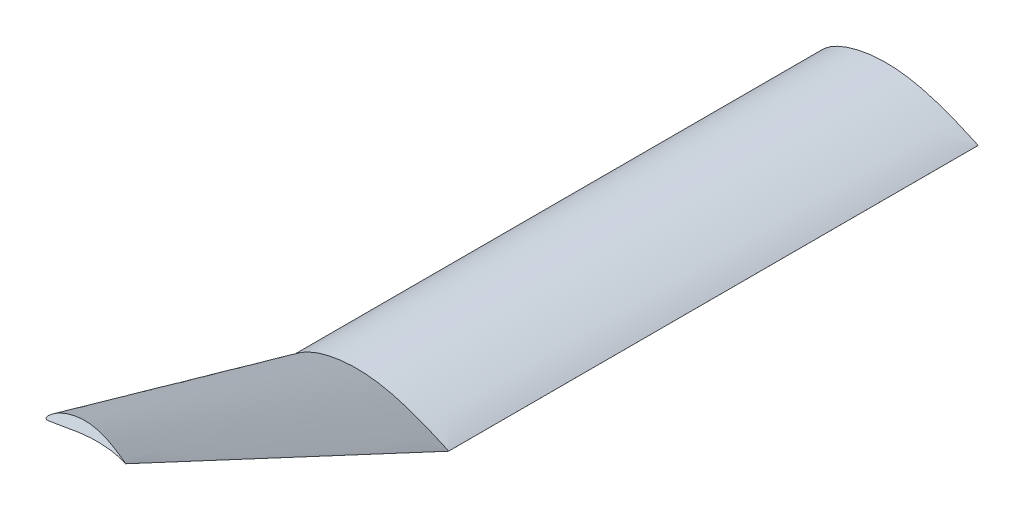
SolidWorks part; units mm, degrees
ref_plane "Front Plane" through (0, 0, 0) normal (0, 0, 1) x (1, 0, 0)
ref_plane "Top Plane" through (0, 0, 0) normal (0, 1, 0) x (1, 0, 0)
ref_plane "Right Plane" through (0, 0, 0) normal (1, 0, 0) x (0, 0, -1)
curve "Curve1"
curve "Curve6"
curve "Curve7"
curve "Curve8"
sketch "Sketch3" plane through (0, 0, 0) normal (0, 0, 1) x (1, 0, 0)
  line L0 (0, 0) -> (50, 0) construction
  line L1 (0.2298, 0.0405) -> (0.2298, 0.0158) construction
  line L2 (0.1804, 0.0405) -> (0.2298, 0.0405)
  line L3 (0.1804, 0.0405) -> (0.1804, -0.0089)
  line L4 (0.1804, -0.0089) -> (0.2298, -0.0089)
  line L5 (0.2298, 0.0405) -> (0.2298, -0.0089)
  line L6 (0.4642, 0.0242) -> (0.4889, 0.0242)
  line L7 (0.4642, 0.0242) -> (0.4642, -0.0005)
  line L8 (0.4642, -0.0005) -> (0.4889, -0.0005)
  line L9 (0.4889, 0.0242) -> (0.4889, -0.0005)
  line L10 (0.2298, 0.0158) -> (0.2146, 0.0158) construction
  line L11 (0.2146, 0.0158) -> (0.2146, 0.0405) construction
  line L12 (0.2146, 0.0405) -> (0.2298, 0.0405) construction
  line L13 (0, 0) -> (500, 0) construction
  line L14 (0.1804, 0.0458) -> (0.1804, -0.0178) construction
  line L15 (0, 0) -> (0, -165.9812) construction
  line L16 (0, -165.9812) -> (300, -165.9812) construction
  line L17 (72.7802, 36.2202) -> (92.7802, 36.2202) construction
  line L18 (70.2802, 13.7202) -> (95.2802, 13.7202)
  line L19 (70.2802, 13.7202) -> (70.2802, 38.7202)
  line L20 (70.2802, 38.7202) -> (95.2802, 38.7202)
  line L21 (95.2802, 13.7202) -> (95.2802, 38.7202)
  line L22 (92.7802, 16.2202) -> (92.7802, 36.2202) construction
  line L23 (72.7802, 16.2202) -> (92.7802, 16.2202) construction
  line L24 (72.7802, 16.2202) -> (72.7802, 36.2202) construction
  line L25 (300, -0.018) -> (300, 0.015)
  line L26 (172.9506, 31.8748) -> (182.9506, 31.8748)
  line L27 (172.9506, 31.8748) -> (172.9506, 21.8748)
  line L28 (172.9506, 21.8748) -> (182.9506, 21.8748)
  line L29 (182.9506, 31.8748) -> (182.9506, 21.8748)
  spline S0 degree 3 poles (1.0002, -0.0023) (1, 0) (1.0002, 0.0023) (0.9919, 0.0001) (0.9849, 0.0027) (0.9729, 0.003) (0.9609, 0.0043) (0.9483, 0.0054) (0.9357, 0.0065) (0.9231, 0.0077) (0.9104, 0.0088) (0.8978, 0.01) (0.8852, 0.0111) (0.8725, 0.0123) (0.8599, 0.0134) (0.8473, 0.0146) (0.8347, 0.0157) (0.8221, 0.0168) (0.8094, 0.0179) (0.7968, 0.019) (0.7842, 0.0201) (0.7716, 0.0211) (0.759, 0.0222) (0.7464, 0.0232) (0.7337, 0.0243) (0.7211, 0.0253) (0.7085, 0.0263) (0.6959, 0.0273) (0.6833, 0.0283) (0.6706, 0.0293) (0.658, 0.0303) (0.6454, 0.0313) (0.6328, 0.0322) (0.6202, 0.0331) (0.6076, 0.0341) (0.595, 0.035) (0.5823, 0.0358) (0.5697, 0.0367) (0.5571, 0.0375) (0.5446, 0.0384) (0.532, 0.0392) (0.5194, 0.0399) (0.5068, 0.0407) (0.4942, 0.0414) (0.4816, 0.0421) (0.469, 0.0427) (0.4565, 0.0434) (0.4439, 0.044) (0.4313, 0.0445) (0.4188, 0.0451) (0.4062, 0.0456) (0.3936, 0.046) (0.3811, 0.0464) (0.3685, 0.0468) (0.356, 0.0472) (0.3435, 0.0475) (0.3309, 0.0477) (0.3184, 0.0479) (0.3059, 0.0481) (0.2934, 0.0482) (0.2809, 0.0482) (0.2685, 0.0482) (0.256, 0.0481) (0.2436, 0.0479) (0.2312, 0.0477) (0.2189, 0.0474) (0.2065, 0.047) (0.1942, 0.0465) (0.182, 0.0459) (0.1698, 0.0452) (0.1576, 0.0444) (0.1456, 0.0434) (0.1336, 0.0423) (0.1217, 0.0411) (0.1099, 0.0397) (0.0983, 0.038) (0.0868, 0.0362) (0.0756, 0.0342) (0.0647, 0.0319) (0.0541, 0.0294) (0.0441, 0.0266) (0.0348, 0.0236) (0.0266, 0.0205) (0.0197, 0.0175) (0.0142, 0.0146) (0.0101, 0.012) (0.007, 0.0098) (0.0047, 0.0078) (0.003, 0.006) (0.0018, 0.0045) (0.0009, 0.003) (0.0003, 0.0017) (0, 0.0004) (0, -0.0008) (0.0005, -0.0021) (0.0015, -0.0032) (0.0028, -0.0043) (0.0046, -0.0054) (0.0068, -0.0066) (0.0097, -0.0078) (0.0135, -0.0091) (0.0186, -0.0106) (0.0252, -0.0121) (0.0334, -0.0135) (0.043, -0.0148) (0.0536, -0.0159) (0.0648, -0.0167) (0.0764, -0.0173) (0.0882, -0.0177) (0.1003, -0.018) (0.1125, -0.0182) (0.1247, -0.0183) (0.1371, -0.0183) (0.1495, -0.0182) (0.162, -0.0181) (0.1745, -0.0179) (0.187, -0.0176) (0.1996, -0.0174) (0.2122, -0.0171) (0.2248, -0.0167) (0.2375, -0.0164) (0.2501, -0.016) (0.2628, -0.0156) (0.2755, -0.0152) (0.2882, -0.0147) (0.3009, -0.0143) (0.3136, -0.0139) (0.3263, -0.0134) (0.339, -0.0129) (0.3517, -0.0125) (0.3644, -0.012) (0.3771, -0.0116) (0.3897, -0.0111) (0.4024, -0.0106) (0.4151, -0.0102) (0.4277, -0.0098) (0.4404, -0.0093) (0.4531, -0.0089) (0.4657, -0.0085) (0.4784, -0.0081) (0.4911, -0.0077) (0.5037, -0.0073) (0.5164, -0.0069) (0.5291, -0.0066) (0.5417, -0.0062) (0.5544, -0.0059) (0.5671, -0.0055) (0.5798, -0.0052) (0.5924, -0.0049) (0.6051, -0.0046) (0.6178, -0.0044) (0.6304, -0.0041) (0.6431, -0.0039) (0.6558, -0.0036) (0.6685, -0.0034) (0.6811, -0.0032) (0.6938, -0.003) (0.7065, -0.0029) (0.7192, -0.0027) (0.7318, -0.0026) (0.7445, -0.0024) (0.7572, -0.0023) (0.7699, -0.0022) (0.7826, -0.0021) (0.7953, -0.002) (0.8079, -0.0019) (0.8206, -0.0019) (0.8333, -0.0018) (0.846, -0.0017) (0.8588, -0.0017) (0.8715, -0.0016) (0.8842, -0.0015) (0.8969, -0.0015) (0.9096, -0.0014) (0.9223, -0.0013) (0.935, -0.0012) (0.9477, -0.0011) (0.9604, -0.0011) (0.9725, -0.0007) (0.9848, -0.0014) (0.9918, 0.0007) (1.0002, -0.0023) (1, 0) (1.0002, 0.0023) knots -0.007874 -0.002894 -0.000332 0 0.000332 0.002885 0.007815 0.013623 0.01978 0.026037 0.032316 0.038604 0.044895 0.051184 0.057469 0.06375 0.070028 0.076304 0.082578 0.088851 0.095124 0.101396 0.107668 0.113941 0.120213 0.126487 0.132762 0.139036 0.145311 0.151585 0.157859 0.16413 0.170401 0.17667 0.182937 0.189202 0.195466 0.201728 0.207987 0.214245 0.2205 0.226754 0.233005 0.239253 0.2455 0.251744 0.257986 0.264226 0.270464 0.2767 0.282933 0.289165 0.295394 0.30162 0.307843 0.314063 0.32028 0.326491 0.332699 0.3389 0.345096 0.351285 0.357467 0.363641 0.369805 0.375959 0.382101 0.38823 0.394345 0.400443 0.406521 0.412577 0.418607 0.424607 0.430573 0.436498 0.442374 0.448192 0.453938 0.459595 0.465142 0.470542 0.475738 0.480625 0.48504 0.488808 0.491844 0.494208 0.496047 0.497501 0.498679 0.499657 0.500486 0.501199 0.501823 0.502412 0.503041 0.50376 0.504602 0.505602 0.50682 0.508337 0.510284 0.512841 0.516185 0.520365 0.525232 0.530552 0.536146 0.541914 0.547804 0.553781 0.559821 0.565909 0.57203 0.578179 0.584352 0.590546 0.596759 0.60299 0.609237 0.615497 0.621768 0.62805 0.634339 0.640634 0.646932 0.653231 0.659529 0.665824 0.672115 0.678404 0.684692 0.690977 0.69726 0.703542 0.709822 0.716099 0.722375 0.728651 0.734927 0.741206 0.747487 0.753768 0.76005 0.766331 0.772611 0.778892 0.785172 0.791451 0.79773 0.804009 0.810289 0.816569 0.822848 0.829126 0.835406 0.841685 0.847965 0.854245 0.860527 0.866808 0.87309 0.879373 0.885657 0.891942 0.898228 0.904515 0.910804 0.917095 0.923389 0.929686 0.935986 0.942288 0.948588 0.954885 0.961183 0.96748 0.973774 0.980051 0.986247 0.992126 0.997106 0.999668 1 1.000332 1.002885 1.007815 only from (1, 0) to (1, 0) construction
  spline S1 degree 3 poles (1.0002, -0.0023) (1, 0) (1.0002, 0.0023) (0.9919, 0.0001) (0.9849, 0.0027) (0.9729, 0.003) (0.9609, 0.0043) (0.9483, 0.0054) (0.9357, 0.0065) (0.9231, 0.0077) (0.9104, 0.0088) (0.8978, 0.01) (0.8852, 0.0111) (0.8725, 0.0123) (0.8599, 0.0134) (0.8473, 0.0146) (0.8347, 0.0157) (0.8221, 0.0168) (0.8094, 0.0179) (0.7968, 0.019) (0.7842, 0.0201) (0.7716, 0.0211) (0.759, 0.0222) (0.7464, 0.0232) (0.7337, 0.0243) (0.7211, 0.0253) (0.7085, 0.0263) (0.6959, 0.0273) (0.6833, 0.0283) (0.6706, 0.0293) (0.658, 0.0303) (0.6454, 0.0313) (0.6328, 0.0322) (0.6202, 0.0331) (0.6076, 0.0341) (0.595, 0.035) (0.5823, 0.0358) (0.5697, 0.0367) (0.5571, 0.0375) (0.5446, 0.0384) (0.532, 0.0392) (0.5194, 0.0399) (0.5068, 0.0407) (0.4942, 0.0414) (0.4816, 0.0421) (0.469, 0.0427) (0.4565, 0.0434) (0.4439, 0.044) (0.4313, 0.0445) (0.4188, 0.0451) (0.4062, 0.0456) (0.3936, 0.046) (0.3811, 0.0464) (0.3685, 0.0468) (0.356, 0.0472) (0.3435, 0.0475) (0.3309, 0.0477) (0.3184, 0.0479) (0.3059, 0.0481) (0.2934, 0.0482) (0.2809, 0.0482) (0.2685, 0.0482) (0.256, 0.0481) (0.2436, 0.0479) (0.2312, 0.0477) (0.2189, 0.0474) (0.2065, 0.047) (0.1942, 0.0465) (0.182, 0.0459) (0.1698, 0.0452) (0.1576, 0.0444) (0.1456, 0.0434) (0.1336, 0.0423) (0.1217, 0.0411) (0.1099, 0.0397) (0.0983, 0.038) (0.0868, 0.0362) (0.0756, 0.0342) (0.0647, 0.0319) (0.0541, 0.0294) (0.0441, 0.0266) (0.0348, 0.0236) (0.0266, 0.0205) (0.0197, 0.0175) (0.0142, 0.0146) (0.0101, 0.012) (0.007, 0.0098) (0.0047, 0.0078) (0.003, 0.006) (0.0018, 0.0045) (0.0009, 0.003) (0.0003, 0.0017) (0, 0.0004) (0, -0.0008) (0.0005, -0.0021) (0.0015, -0.0032) (0.0028, -0.0043) (0.0046, -0.0054) (0.0068, -0.0066) (0.0097, -0.0078) (0.0135, -0.0091) (0.0186, -0.0106) (0.0252, -0.0121) (0.0334, -0.0135) (0.043, -0.0148) (0.0536, -0.0159) (0.0648, -0.0167) (0.0764, -0.0173) (0.0882, -0.0177) (0.1003, -0.018) (0.1125, -0.0182) (0.1247, -0.0183) (0.1371, -0.0183) (0.1495, -0.0182) (0.162, -0.0181) (0.1745, -0.0179) (0.187, -0.0176) (0.1996, -0.0174) (0.2122, -0.0171) (0.2248, -0.0167) (0.2375, -0.0164) (0.2501, -0.016) (0.2628, -0.0156) (0.2755, -0.0152) (0.2882, -0.0147) (0.3009, -0.0143) (0.3136, -0.0139) (0.3263, -0.0134) (0.339, -0.0129) (0.3517, -0.0125) (0.3644, -0.012) (0.3771, -0.0116) (0.3897, -0.0111) (0.4024, -0.0106) (0.4151, -0.0102) (0.4277, -0.0098) (0.4404, -0.0093) (0.4531, -0.0089) (0.4657, -0.0085) (0.4784, -0.0081) (0.4911, -0.0077) (0.5037, -0.0073) (0.5164, -0.0069) (0.5291, -0.0066) (0.5417, -0.0062) (0.5544, -0.0059) (0.5671, -0.0055) (0.5798, -0.0052) (0.5924, -0.0049) (0.6051, -0.0046) (0.6178, -0.0044) (0.6304, -0.0041) (0.6431, -0.0039) (0.6558, -0.0036) (0.6685, -0.0034) (0.6811, -0.0032) (0.6938, -0.003) (0.7065, -0.0029) (0.7192, -0.0027) (0.7318, -0.0026) (0.7445, -0.0024) (0.7572, -0.0023) (0.7699, -0.0022) (0.7826, -0.0021) (0.7953, -0.002) (0.8079, -0.0019) (0.8206, -0.0019) (0.8333, -0.0018) (0.846, -0.0017) (0.8588, -0.0017) (0.8715, -0.0016) (0.8842, -0.0015) (0.8969, -0.0015) (0.9096, -0.0014) (0.9223, -0.0013) (0.935, -0.0012) (0.9477, -0.0011) (0.9604, -0.0011) (0.9725, -0.0007) (0.9848, -0.0014) (0.9918, 0.0007) (1.0002, -0.0023) (1, 0) (1.0002, 0.0023) knots -0.007874 -0.002894 -0.000332 0 0.000332 0.002885 0.007815 0.013623 0.01978 0.026037 0.032316 0.038604 0.044895 0.051184 0.057469 0.06375 0.070028 0.076304 0.082578 0.088851 0.095124 0.101396 0.107668 0.113941 0.120213 0.126487 0.132762 0.139036 0.145311 0.151585 0.157859 0.16413 0.170401 0.17667 0.182937 0.189202 0.195466 0.201728 0.207987 0.214245 0.2205 0.226754 0.233005 0.239253 0.2455 0.251744 0.257986 0.264226 0.270464 0.2767 0.282933 0.289165 0.295394 0.30162 0.307843 0.314063 0.32028 0.326491 0.332699 0.3389 0.345096 0.351285 0.357467 0.363641 0.369805 0.375959 0.382101 0.38823 0.394345 0.400443 0.406521 0.412577 0.418607 0.424607 0.430573 0.436498 0.442374 0.448192 0.453938 0.459595 0.465142 0.470542 0.475738 0.480625 0.48504 0.488808 0.491844 0.494208 0.496047 0.497501 0.498679 0.499657 0.500486 0.501199 0.501823 0.502412 0.503041 0.50376 0.504602 0.505602 0.50682 0.508337 0.510284 0.512841 0.516185 0.520365 0.525232 0.530552 0.536146 0.541914 0.547804 0.553781 0.559821 0.565909 0.57203 0.578179 0.584352 0.590546 0.596759 0.60299 0.609237 0.615497 0.621768 0.62805 0.634339 0.640634 0.646932 0.653231 0.659529 0.665824 0.672115 0.678404 0.684692 0.690977 0.69726 0.703542 0.709822 0.716099 0.722375 0.728651 0.734927 0.741206 0.747487 0.753768 0.76005 0.766331 0.772611 0.778892 0.785172 0.791451 0.79773 0.804009 0.810289 0.816569 0.822848 0.829126 0.835406 0.841685 0.847965 0.854245 0.860527 0.866808 0.87309 0.879373 0.885657 0.891942 0.898228 0.904515 0.910804 0.917095 0.923389 0.929686 0.935986 0.942288 0.948588 0.954885 0.961183 0.96748 0.973774 0.980051 0.986247 0.992126 0.997106 0.999668 1 1.000332 1.002885 1.007815 only from (1, 0) to (1, 0) construction
  spline S2 degree 3 poles (500.0959, -1.1537) (499.9892, 0.0005) (500.0921, 1.1423) (495.9334, 0.0411) (492.471, 1.3334) (486.441, 1.5239) (480.4457, 2.1624) (474.1516, 2.6955) (467.853, 3.2724) (461.5326, 3.8433) (455.2123, 4.419) (448.8921, 4.9943) (442.5755, 5.5699) (436.262, 6.142) (429.9511, 6.7101) (423.6424, 7.2769) (417.3349, 7.8378) (411.0282, 8.3936) (404.7219, 8.9456) (398.4154, 9.4908) (392.1084, 10.0313) (385.8007, 10.567) (379.4922, 11.0968) (373.1826, 11.6221) (366.8717, 12.1412) (360.56, 12.6562) (354.2482, 13.167) (347.9364, 13.6717) (341.6252, 14.172) (335.3149, 14.6658) (329.0056, 15.1544) (322.6972, 15.6341) (316.3902, 16.1098) (310.0841, 16.5743) (303.7793, 17.0336) (297.4758, 17.4828) (291.1738, 17.9236) (284.8734, 18.3542) (278.5742, 18.7741) (272.2766, 19.1842) (265.9803, 19.5806) (259.6857, 19.9669) (253.3925, 20.3385) (247.1009, 20.6976) (240.8108, 21.0438) (234.5219, 21.3728) (228.2344, 21.6877) (221.9482, 21.986) (215.6634, 22.269) (209.38, 22.5336) (203.0985, 22.7823) (196.8192, 23.011) (190.5422, 23.2214) (184.2678, 23.4112) (177.9968, 23.5814) (171.7294, 23.7279) (165.4666, 23.8538) (159.2085, 23.9536) (152.9563, 24.0285) (146.7104, 24.0763) (140.4718, 24.0951) (134.2418, 24.0833) (128.0212, 24.0398) (121.8114, 23.9589) (115.6139, 23.8431) (109.4305, 23.6857) (103.2636, 23.4864) (97.1155, 23.2386) (90.9895, 22.9417) (84.8889, 22.5902) (78.8182, 22.1795) (72.7826, 21.7035) (66.7884, 21.1583) (60.844, 20.5334) (54.9591, 19.8268) (49.1468, 19.0246) (43.424, 18.1218) (37.8124, 17.1067) (32.343, 15.9694) (27.0604, 14.7062) (22.0393, 13.3164) (17.395, 11.8221) (13.2795, 10.2688) (9.8299, 8.731) (7.0994, 7.2913) (5.0301, 6.0034) (3.4945, 4.8762) (2.3559, 3.8907) (1.5099, 3.0166) (0.8848, 2.2285) (0.4335, 1.5087) (0.1314, 0.8425) (-0.0182, 0.2062) (0.0104, -0.4232) (0.2632, -1.0376) (0.7397, -1.6094) (1.4111, -2.154) (2.2826, -2.7045) (3.4007, -3.2811) (4.8511, -3.898) (6.7651, -4.5654) (9.3055, -5.2886) (12.6143, -6.039) (16.7206, -6.7632) (21.5126, -7.4019) (26.7966, -7.9252) (32.394, -8.3361) (38.1897, -8.6462) (44.118, -8.8675) (50.1404, -9.0195) (56.2306, -9.1096) (62.3698, -9.1496) (68.5456, -9.1443) (74.75, -9.104) (80.9785, -9.0332) (87.2282, -8.9364) (93.4969, -8.818) (99.783, -8.6804) (106.0845, -8.5272) (112.3995, -8.3597) (118.7258, -8.1811) (125.0618, -7.9892) (131.4053, -7.7924) (137.7541, -7.5838) (144.1059, -7.37) (150.4584, -7.1501) (156.8097, -6.9267) (163.1584, -6.6992) (169.5042, -6.4709) (175.8475, -6.2404) (182.1887, -6.0105) (188.5278, -5.7806) (194.865, -5.5531) (201.2002, -5.325) (207.5338, -5.1031) (213.8656, -4.8806) (220.1961, -4.6635) (226.5264, -4.4495) (232.8578, -4.2412) (239.1911, -4.0373) (245.5262, -3.8375) (251.8626, -3.6436) (258.1993, -3.458) (264.5356, -3.2755) (270.8718, -3.1019) (277.2076, -2.9318) (283.5434, -2.7691) (289.8787, -2.6119) (296.2141, -2.4645) (302.5496, -2.3201) (308.8856, -2.184) (315.2216, -2.0569) (321.5574, -1.9335) (327.8933, -1.8191) (334.2294, -1.7131) (340.5661, -1.6125) (346.9033, -1.5208) (353.2413, -1.4364) (359.58, -1.3587) (365.9191, -1.2888) (372.2588, -1.223) (378.5993, -1.1661) (384.9408, -1.1114) (391.2835, -1.0632) (397.6273, -1.0167) (403.9727, -0.9749) (410.3197, -0.9366) (416.669, -0.8947) (423.021, -0.8606) (429.376, -0.8257) (435.7337, -0.7924) (442.0922, -0.7597) (448.4498, -0.726) (454.8061, -0.6894) (461.1609, -0.6473) (467.5175, -0.6036) (473.8564, -0.5446) (480.2008, -0.5303) (486.2618, -0.3697) (492.3763, -0.6848) (495.8827, 0.3278) (500.0959, -1.1537) (499.9892, 0.0005) (500.0921, 1.1423) knots -0.007874 -0.002894 -0.000332 0 0.000332 0.002885 0.007815 0.013623 0.01978 0.026037 0.032316 0.038604 0.044895 0.051184 0.057469 0.06375 0.070028 0.076304 0.082578 0.088851 0.095124 0.101396 0.107668 0.113941 0.120213 0.126487 0.132762 0.139036 0.145311 0.151585 0.157859 0.16413 0.170401 0.17667 0.182937 0.189202 0.195466 0.201728 0.207987 0.214245 0.2205 0.226754 0.233005 0.239253 0.2455 0.251744 0.257986 0.264226 0.270464 0.2767 0.282933 0.289165 0.295394 0.30162 0.307843 0.314063 0.32028 0.326491 0.332699 0.3389 0.345096 0.351285 0.357467 0.363641 0.369805 0.375959 0.382101 0.38823 0.394345 0.400443 0.406521 0.412577 0.418607 0.424607 0.430573 0.436498 0.442374 0.448192 0.453938 0.459595 0.465142 0.470542 0.475738 0.480625 0.48504 0.488808 0.491844 0.494208 0.496047 0.497501 0.498679 0.499657 0.500486 0.501199 0.501823 0.502412 0.503041 0.50376 0.504602 0.505602 0.50682 0.508337 0.510284 0.512841 0.516185 0.520365 0.525232 0.530552 0.536146 0.541914 0.547804 0.553781 0.559821 0.565909 0.57203 0.578179 0.584352 0.590546 0.596759 0.60299 0.609237 0.615497 0.621768 0.62805 0.634339 0.640634 0.646932 0.653231 0.659529 0.665824 0.672115 0.678404 0.684692 0.690977 0.69726 0.703542 0.709822 0.716099 0.722375 0.728651 0.734927 0.741206 0.747487 0.753768 0.76005 0.766331 0.772611 0.778892 0.785172 0.791451 0.79773 0.804009 0.810289 0.816569 0.822848 0.829126 0.835406 0.841685 0.847965 0.854245 0.860527 0.866808 0.87309 0.879373 0.885657 0.891942 0.898228 0.904515 0.910804 0.917095 0.923389 0.929686 0.935986 0.942288 0.948588 0.954885 0.961183 0.96748 0.973774 0.980051 0.986247 0.992126 0.997106 0.999668 1 1.000332 1.002885 1.007815 only from (500, 0) to (500, 0) construction
  spline S3 degree 3 poles (0.0009, 0.0052) (-0.0004, 0.0004) (0.0009, -0.0041) (0.0046, -0.0077) (0.01, -0.0109) (0.0176, -0.0135) (0.0271, -0.0161) (0.0387, -0.0182) (0.0522, -0.0201) (0.0676, -0.0217) (0.0848, -0.023) (0.1039, -0.024) (0.1246, -0.0248) (0.147, -0.0252) (0.1708, -0.0253) (0.1961, -0.0249) (0.2226, -0.0244) (0.2504, -0.0233) (0.2792, -0.022) (0.3089, -0.0201) (0.3395, -0.018) (0.3708, -0.0154) (0.4026, -0.0128) (0.4348, -0.0098) (0.4673, -0.0069) (0.5, -0.0039) (0.5326, -0.0011) (0.5652, 0.0016) (0.5974, 0.004) (0.6292, 0.0062) (0.6605, 0.0079) (0.6911, 0.0092) (0.7208, 0.0102) (0.7496, 0.0109) (0.7774, 0.0112) (0.8039, 0.0112) (0.8292, 0.0108) (0.8531, 0.0102) (0.8754, 0.0093) (0.8961, 0.0083) (0.9151, 0.0072) (0.9324, 0.006) (0.9478, 0.0048) (0.9613, 0.0036) (0.9728, 0.0025) (0.9823, 0.0014) (0.9896, 0.0009) (0.9953, 0) (0.9977, 0.0003) (1.0006, -0.0001) (0.9978, 0.0008) (0.9953, 0.0005) (0.9896, 0.0024) (0.9823, 0.0038) (0.9728, 0.0059) (0.9613, 0.0083) (0.9478, 0.0111) (0.9324, 0.0142) (0.9151, 0.0177) (0.8961, 0.0215) (0.8754, 0.0255) (0.8531, 0.0298) (0.8292, 0.0342) (0.804, 0.0388) (0.7774, 0.0435) (0.7497, 0.0482) (0.7209, 0.0527) (0.6911, 0.057) (0.6605, 0.0611) (0.6292, 0.0649) (0.5974, 0.0683) (0.5652, 0.0714) (0.5327, 0.074) (0.5, 0.0763) (0.4674, 0.0782) (0.4348, 0.0796) (0.4026, 0.0805) (0.3708, 0.0807) (0.3395, 0.0805) (0.3089, 0.0796) (0.2792, 0.0783) (0.2503, 0.0762) (0.2226, 0.0737) (0.196, 0.0706) (0.1707, 0.0671) (0.1469, 0.063) (0.1245, 0.0586) (0.1038, 0.0538) (0.0847, 0.0488) (0.0675, 0.0434) (0.052, 0.0379) (0.0385, 0.0321) (0.027, 0.0264) (0.0174, 0.0207) (0.01, 0.0151) (0.0045, 0.01) (0.0009, 0.0052) (-0.0004, 0.0004) (0.0009, -0.0041) knots -0.00884 -0.005198 -0.002428 0 0.00188 0.004212 0.007287 0.011193 0.016028 0.021799 0.028506 0.036135 0.044658 0.05404 0.064256 0.075258 0.087001 0.099438 0.112517 0.126192 0.1404 0.155081 0.170175 0.18562 0.201344 0.217287 0.233363 0.249508 0.265648 0.281715 0.297638 0.313339 0.328759 0.343831 0.358493 0.372688 0.386355 0.39943 0.411868 0.423614 0.434623 0.444843 0.454228 0.462746 0.470357 0.477022 0.482719 0.487411 0.491081 0.493714 0.495293 0.495821 0.496379 0.497969 0.500662 0.504411 0.509181 0.514974 0.521753 0.529496 0.538165 0.547715 0.558116 0.569314 0.581261 0.593902 0.607179 0.621035 0.635401 0.650209 0.6654 0.680908 0.696666 0.712615 0.72868 0.744799 0.760906 0.776932 0.792816 0.808483 0.82388 0.838944 0.853614 0.86784 0.881563 0.894727 0.907286 0.919199 0.930414 0.940893 0.950586 0.959485 0.967557 0.974773 0.981115 0.986579 0.99116 0.994802 0.997572 1 1.00188 1.004212 1.007287 only from (0, 0) to (0, 0) construction
  spline S4 degree 3 poles (0.0009, 0.0052) (-0.0004, 0.0004) (0.0009, -0.0041) (0.0046, -0.0077) (0.01, -0.0109) (0.0176, -0.0135) (0.0271, -0.0161) (0.0387, -0.0182) (0.0522, -0.0201) (0.0676, -0.0217) (0.0848, -0.023) (0.1039, -0.024) (0.1246, -0.0248) (0.147, -0.0252) (0.1708, -0.0253) (0.1961, -0.0249) (0.2226, -0.0244) (0.2504, -0.0233) (0.2792, -0.022) (0.3089, -0.0201) (0.3395, -0.018) (0.3708, -0.0154) (0.4026, -0.0128) (0.4348, -0.0098) (0.4673, -0.0069) (0.5, -0.0039) (0.5326, -0.0011) (0.5652, 0.0016) (0.5974, 0.004) (0.6292, 0.0062) (0.6605, 0.0079) (0.6911, 0.0092) (0.7208, 0.0102) (0.7496, 0.0109) (0.7774, 0.0112) (0.8039, 0.0112) (0.8292, 0.0108) (0.8531, 0.0102) (0.8754, 0.0093) (0.8961, 0.0083) (0.9151, 0.0072) (0.9324, 0.006) (0.9478, 0.0048) (0.9613, 0.0036) (0.9728, 0.0025) (0.9823, 0.0014) (0.9896, 0.0009) (0.9953, 0) (0.9977, 0.0003) (1.0006, -0.0001) (0.9978, 0.0008) (0.9953, 0.0005) (0.9896, 0.0024) (0.9823, 0.0038) (0.9728, 0.0059) (0.9613, 0.0083) (0.9478, 0.0111) (0.9324, 0.0142) (0.9151, 0.0177) (0.8961, 0.0215) (0.8754, 0.0255) (0.8531, 0.0298) (0.8292, 0.0342) (0.804, 0.0388) (0.7774, 0.0435) (0.7497, 0.0482) (0.7209, 0.0527) (0.6911, 0.057) (0.6605, 0.0611) (0.6292, 0.0649) (0.5974, 0.0683) (0.5652, 0.0714) (0.5327, 0.074) (0.5, 0.0763) (0.4674, 0.0782) (0.4348, 0.0796) (0.4026, 0.0805) (0.3708, 0.0807) (0.3395, 0.0805) (0.3089, 0.0796) (0.2792, 0.0783) (0.2503, 0.0762) (0.2226, 0.0737) (0.196, 0.0706) (0.1707, 0.0671) (0.1469, 0.063) (0.1245, 0.0586) (0.1038, 0.0538) (0.0847, 0.0488) (0.0675, 0.0434) (0.052, 0.0379) (0.0385, 0.0321) (0.027, 0.0264) (0.0174, 0.0207) (0.01, 0.0151) (0.0045, 0.01) (0.0009, 0.0052) (-0.0004, 0.0004) (0.0009, -0.0041) knots -0.00884 -0.005198 -0.002428 0 0.00188 0.004212 0.007287 0.011193 0.016028 0.021799 0.028506 0.036135 0.044658 0.05404 0.064256 0.075258 0.087001 0.099438 0.112517 0.126192 0.1404 0.155081 0.170175 0.18562 0.201344 0.217287 0.233363 0.249508 0.265648 0.281715 0.297638 0.313339 0.328759 0.343831 0.358493 0.372688 0.386355 0.39943 0.411868 0.423614 0.434623 0.444843 0.454228 0.462746 0.470357 0.477022 0.482719 0.487411 0.491081 0.493714 0.495293 0.495821 0.496379 0.497969 0.500662 0.504411 0.509181 0.514974 0.521753 0.529496 0.538165 0.547715 0.558116 0.569314 0.581261 0.593902 0.607179 0.621035 0.635401 0.650209 0.6654 0.680908 0.696666 0.712615 0.72868 0.744799 0.760906 0.776932 0.792816 0.808483 0.82388 0.838944 0.853614 0.86784 0.881563 0.894727 0.907286 0.919199 0.930414 0.940893 0.950586 0.959485 0.967557 0.974773 0.981115 0.986579 0.99116 0.994802 0.997572 1 1.00188 1.004212 1.007287 only from (0, 0) to (0, 0)
  spline S6 degree 3 poles (1643.0294, 2510.6121) (-0.9132, -4.9999) (1.4845, -0.2863) (0.9897, 0.0065) (0.9795, 0.0117) (0.966, 0.0177) (0.9494, 0.025) (0.9297, 0.0336) (0.8975, 0.0473) (0.8617, 0.0622) (0.8225, 0.0776) (0.79, 0.0897) (0.7558, 0.1017) (0.7079, 0.1172) (0.6584, 0.1311) (0.6078, 0.1427) (0.5695, 0.1499) (0.5311, 0.1556) (0.4927, 0.1597) (0.4545, 0.162) (0.4165, 0.1627) (0.3791, 0.1616) (0.3305, 0.1581) (0.2833, 0.1514) (0.2379, 0.1418) (0.2058, 0.1335) (0.1754, 0.124) (0.1469, 0.1134) (0.1204, 0.1018) (0.0962, 0.0895) (0.0744, 0.0767) (0.0552, 0.0638) (0.0386, 0.051) (0.0247, 0.0387) (0.0137, 0.027) (0.0057, 0.0163) (0.0011, 0.0075) (-0.0003, 0.0005) (0.0007, -0.0053) (0.0058, -0.01) (0.0142, -0.0123) (0.0253, -0.0129) (0.0391, -0.0122) (0.0556, -0.0102) (0.0748, -0.0075) (0.0966, -0.0042) (0.1207, -0.0007) (0.1472, 0.0033) (0.1757, 0.0076) (0.2172, 0.0138) (0.2609, 0.02) (0.3311, 0.0293) (0.3922, 0.0363) (0.4672, 0.043) (0.531, 0.0474) (0.5949, 0.0495) (0.6458, 0.0495) (0.6833, 0.0486) (0.7201, 0.0469) (0.7557, 0.0444) (0.7899, 0.0412) (0.8225, 0.0376) (0.853, 0.0334) (0.8812, 0.0289) (0.9069, 0.0241) (0.9297, 0.0193) (0.9494, 0.0145) (0.966, 0.0098) (0.9793, 0.0054) (0.9895, 0.0024) (1.5167, -0.1309) (3.0282, 4.3648) (-623.5231, -2934.0731) knots -0.813001 -0.813001 -0.813001 -0.813001 0.001413 0.005226 0.010781 0.017816 0.026461 0.036791 0.048686 0.076639 0.092363 0.109003 0.126387 0.144339 0.181313 0.200023 0.218713 0.237261 0.255692 0.274037 0.292193 0.310133 0.327788 0.362002 0.378421 0.394287 0.409543 0.424114 0.437938 0.450942 0.463044 0.474154 0.484165 0.493024 0.500713 0.507126 0.51213 0.514904 0.517171 0.520262 0.524245 0.529498 0.536092 0.544061 0.553363 0.563905 0.575615 0.58842 0.602227 0.616944 0.648676 0.665501 0.718564 0.736789 0.773513 0.810245 0.828489 0.846493 0.864125 0.881249 0.897725 0.913415 0.928184 0.941897 0.954411 0.965603 0.97535 0.983576 0.990285 0.995433 0.9988 1.769799 1.769799 1.769799 1.769799 only from (1, 0.0001) to (1, -0.0001) construction
  spline S7 degree 3 poles (1, 0.0001) (0.9992, 0.0006) (0.9962, 0.0026) (0.9897, 0.0065) (0.9795, 0.0117) (0.966, 0.0177) (0.9494, 0.025) (0.9297, 0.0336) (0.8975, 0.0473) (0.8617, 0.0622) (0.8225, 0.0776) (0.79, 0.0897) (0.7558, 0.1017) (0.7079, 0.1172) (0.6584, 0.1311) (0.6078, 0.1427) (0.5695, 0.1499) (0.5311, 0.1556) (0.4927, 0.1597) (0.4545, 0.162) (0.4165, 0.1627) (0.3791, 0.1616) (0.3305, 0.1581) (0.2833, 0.1514) (0.2379, 0.1418) (0.2058, 0.1335) (0.1754, 0.124) (0.1469, 0.1134) (0.1204, 0.1018) (0.0962, 0.0895) (0.0744, 0.0767) (0.0552, 0.0638) (0.0386, 0.051) (0.0247, 0.0387) (0.0137, 0.027) (0.0057, 0.0163) (0.0011, 0.0075) (-0.0003, 0.0005) (0.0007, -0.0053) (0.0058, -0.01) (0.0142, -0.0123) (0.0253, -0.0129) (0.0391, -0.0122) (0.0556, -0.0102) (0.0748, -0.0075) (0.0966, -0.0042) (0.1207, -0.0007) (0.1472, 0.0033) (0.1757, 0.0076) (0.2172, 0.0138) (0.2609, 0.02) (0.3311, 0.0293) (0.3922, 0.0363) (0.4672, 0.043) (0.531, 0.0474) (0.5949, 0.0495) (0.6458, 0.0495) (0.6833, 0.0486) (0.7201, 0.0469) (0.7557, 0.0444) (0.7899, 0.0412) (0.8225, 0.0376) (0.853, 0.0334) (0.8812, 0.0289) (0.9069, 0.0241) (0.9297, 0.0193) (0.9494, 0.0145) (0.966, 0.0098) (0.9793, 0.0054) (0.9895, 0.0024) (0.9961, 0.0007) (0.9992, 0.0001) (1, -0.0001) knots 0 0 0 0 0.001413 0.005226 0.010781 0.017816 0.026461 0.036791 0.048686 0.076639 0.092363 0.109003 0.126387 0.144339 0.181313 0.200023 0.218713 0.237261 0.255692 0.274037 0.292193 0.310133 0.327788 0.362002 0.378421 0.394287 0.409543 0.424114 0.437938 0.450942 0.463044 0.474154 0.484165 0.493024 0.500713 0.507126 0.51213 0.514904 0.517171 0.520262 0.524245 0.529498 0.536092 0.544061 0.553363 0.563905 0.575615 0.58842 0.602227 0.616944 0.648676 0.665501 0.718564 0.736789 0.773513 0.810245 0.828489 0.846493 0.864125 0.881249 0.897725 0.913415 0.928184 0.941897 0.954411 0.965603 0.97535 0.983576 0.990285 0.995433 0.9988 1 1 1 1
  spline S8 degree 3 poles (300, 0.015) (299.7549, 0.1803) (298.8485, 0.7916) (296.9058, 1.9408) (293.8466, 3.4981) (289.7862, 5.3006) (284.8109, 7.501) (278.8968, 10.0932) (269.2354, 14.1942) (258.4984, 18.6488) (246.7587, 23.2716) (237.0102, 26.9128) (226.7497, 30.5099) (212.3568, 35.1631) (197.5225, 39.3346) (182.3532, 42.7985) (170.8532, 44.983) (159.3316, 46.6908) (147.8202, 47.91) (136.3478, 48.6095) (124.9585, 48.8071) (113.7162, 48.4849) (99.1486, 47.4166) (84.9892, 45.4203) (71.3746, 42.5477) (61.7481, 40.04) (52.6211, 37.1899) (44.0583, 34.0079) (36.1164, 30.545) (28.8549, 26.8491) (22.3219, 23.0051) (16.5503, 19.1272) (11.572, 15.306) (7.4224, 11.6043) (4.1227, 8.1029) (1.7178, 4.9011) (0.3395, 2.2392) (-0.1024, 0.1583) (0.204, -1.5858) (1.7337, -3.0118) (4.2692, -3.6752) (7.5793, -3.8829) (11.7249, -3.6469) (16.6836, -3.0728) (22.4426, -2.246) (28.9693, -1.2656) (36.224, -0.1978) (44.1511, 0.9911) (52.7004, 2.2732) (65.1658, 4.1342) (78.2672, 6.0122) (99.3394, 8.8005) (117.6535, 10.8907) (140.1569, 12.9054) (159.2914, 14.2176) (178.4661, 14.8407) (193.7325, 14.8395) (205.0007, 14.5833) (216.0252, 14.0626) (226.7164, 13.3188) (236.9837, 12.3748) (246.7404, 11.2771) (255.8965, 10.033) (264.365, 8.6788) (272.0599, 7.2435) (278.9039, 5.7843) (284.8344, 4.3498) (289.7985, 2.9258) (293.7954, 1.6329) (296.8452, 0.7155) (298.8166, 0.2169) (299.7538, 0.0309) (300, -0.018) knots 0 0 0 0 0.001413 0.005226 0.010781 0.017816 0.026461 0.036791 0.048686 0.076639 0.092363 0.109003 0.126387 0.144339 0.181313 0.200023 0.218713 0.237261 0.255692 0.274037 0.292193 0.310133 0.327788 0.362002 0.378421 0.394287 0.409543 0.424114 0.437938 0.450942 0.463044 0.474154 0.484165 0.493024 0.500713 0.507126 0.51213 0.514904 0.517171 0.520262 0.524245 0.529498 0.536092 0.544061 0.553363 0.563905 0.575615 0.58842 0.602227 0.616944 0.648676 0.665501 0.718564 0.736789 0.773513 0.810245 0.828489 0.846493 0.864125 0.881249 0.897725 0.913415 0.928184 0.941897 0.954411 0.965603 0.97535 0.983576 0.990285 0.995433 0.9988 1 1 1 1
  dimension "D1" = 300
  dimension "D2" = 25
  dimension "D3" = 2.5
  dimension "D4" = 20
  dimension "D5" = 10
extrude "Boss-Extrude1" add sketch "Sketch3" along normal blind 1000 contours L25 S8 L3 L2 L5 L4 L26 L29 L28 L27 L6 L9 L8 L7 L21 L18 L19 L20 region at (0.2962, 0.0449, 0) region at (0.1705, -0.0003, 0) region at (0.005, -0.0079, 0) region at (125.7868, 23.7644, 0) region at (0.8963, 0.0231, 0) region at (0.4716, 0.099, 0) region at (0.9981, 0.0004, 0)
sketch "Sketch5" plane through (0, 0, 0) normal (1, 0, 0) x (0, 0, -1)
  line L0 (-1000, 26.2202) -> (-1600, 306.0048) construction
  line L1 (-1000, 26.2202) -> (-928.4406, 26.2202) construction
  line L2 (-1000, 26.2202) -> (-1200.048, 26.2202) construction
  line L4 (0, 13.7202) -> (0, 38.7202)
  line L5 (0, 38.7202) -> (-1000, 38.7202)
  line L6 (-1000, 38.7202) -> (-1000, 13.7202)
  line L7 (-1000, 13.7202) -> (0, 13.7202)
  line L10 (-1000, 38.7202) -> (-1000, 13.7202) construction
  dimension "D2" = 25
  dimension "D3" = 600
  dimension "D1" = 0
ref_plane "Plane1" through (0, 306.0048, 1600) normal (0, 0.4226, 0.9063) x (1, 0, 0)
sketch "Sketch6" plane through (0, 306.0048, 1600) normal (0, 0.4226, 0.9063) x (1, 0, 0)
  line L0 (0, -49.6836) -> (50, -49.6836) construction
  line L13 (0, -49.6836) -> (500, -49.6836) construction
  line L14 (300, -23.7665) -> (150, -23.7665) construction
  line L15 (0, -49.6836) -> (0, -146.6712) construction
  line L16 (0, -146.6712) -> (300, -146.6712) construction
  line L25 (300, -23.7665) -> (300, -23.75)
  line L31 (300, -23.7799) -> (300, -23.75)
  line L32 (300, -23.7799) -> (300, -23.75) construction
  spline S0 degree 3 poles (-457.9361, -49.6859) (-457.9364, -49.6836) (-457.9362, -49.6813) (-457.9445, -49.6835) (-457.9514, -49.6809) (-457.9635, -49.6806) (-457.9754, -49.6793) (-457.988, -49.6782) (-458.0006, -49.6771) (-458.0133, -49.6759) (-458.0259, -49.6748) (-458.0386, -49.6736) (-458.0512, -49.6725) (-458.0638, -49.6713) (-458.0764, -49.6702) (-458.0891, -49.6691) (-458.1017, -49.6679) (-458.1143, -49.6668) (-458.1269, -49.6657) (-458.1395, -49.6646) (-458.1521, -49.6635) (-458.1647, -49.6625) (-458.1774, -49.6614) (-458.19, -49.6604) (-458.2026, -49.6593) (-458.2152, -49.6583) (-458.2278, -49.6573) (-458.2405, -49.6563) (-458.2531, -49.6553) (-458.2657, -49.6543) (-458.2783, -49.6533) (-458.2909, -49.6523) (-458.3036, -49.6514) (-458.3162, -49.6505) (-458.3288, -49.6495) (-458.3414, -49.6486) (-458.354, -49.6478) (-458.3666, -49.6469) (-458.3792, -49.6461) (-458.3918, -49.6452) (-458.4044, -49.6444) (-458.417, -49.6437) (-458.4296, -49.6429) (-458.4421, -49.6422) (-458.4547, -49.6415) (-458.4673, -49.6409) (-458.4799, -49.6402) (-458.4924, -49.6396) (-458.505, -49.6391) (-458.5176, -49.6385) (-458.5301, -49.638) (-458.5427, -49.6376) (-458.5553, -49.6372) (-458.5678, -49.6368) (-458.5803, -49.6364) (-458.5929, -49.6361) (-458.6054, -49.6359) (-458.6179, -49.6357) (-458.6304, -49.6355) (-458.6429, -49.6355) (-458.6554, -49.6354) (-458.6679, -49.6354) (-458.6803, -49.6355) (-458.6927, -49.6357) (-458.7051, -49.6359) (-458.7175, -49.6362) (-458.7298, -49.6366) (-458.7421, -49.6371) (-458.7544, -49.6377) (-458.7666, -49.6384) (-458.7787, -49.6392) (-458.7908, -49.6402) (-458.8028, -49.6413) (-458.8147, -49.6425) (-458.8264, -49.644) (-458.838, -49.6456) (-458.8495, -49.6474) (-458.8607, -49.6494) (-458.8717, -49.6517) (-458.8822, -49.6542) (-458.8923, -49.657) (-458.9016, -49.66) (-458.9098, -49.6631) (-458.9167, -49.6661) (-458.9221, -49.669) (-458.9263, -49.6716) (-458.9294, -49.6739) (-458.9316, -49.6758) (-458.9333, -49.6776) (-458.9346, -49.6791) (-458.9355, -49.6806) (-458.9361, -49.6819) (-458.9364, -49.6832) (-458.9363, -49.6845) (-458.9358, -49.6857) (-458.9349, -49.6868) (-458.9335, -49.6879) (-458.9318, -49.689) (-458.9295, -49.6902) (-458.9266, -49.6914) (-458.9228, -49.6927) (-458.9177, -49.6942) (-458.9111, -49.6957) (-458.9029, -49.6971) (-458.8933, -49.6984) (-458.8827, -49.6995) (-458.8716, -49.7003) (-458.86, -49.7009) (-458.8481, -49.7013) (-458.8361, -49.7016) (-458.8239, -49.7018) (-458.8116, -49.7019) (-458.7992, -49.7019) (-458.7868, -49.7018) (-458.7744, -49.7017) (-458.7619, -49.7015) (-458.7493, -49.7012) (-458.7368, -49.701) (-458.7242, -49.7007) (-458.7115, -49.7003) (-458.6989, -49.7) (-458.6862, -49.6996) (-458.6735, -49.6992) (-458.6608, -49.6988) (-458.6481, -49.6983) (-458.6354, -49.6979) (-458.6227, -49.6975) (-458.61, -49.697) (-458.5973, -49.6965) (-458.5846, -49.6961) (-458.572, -49.6956) (-458.5593, -49.6952) (-458.5466, -49.6947) (-458.5339, -49.6943) (-458.5213, -49.6938) (-458.5086, -49.6934) (-458.4959, -49.6929) (-458.4833, -49.6925) (-458.4706, -49.6921) (-458.458, -49.6917) (-458.4453, -49.6913) (-458.4326, -49.6909) (-458.4199, -49.6905) (-458.4073, -49.6902) (-458.3946, -49.6898) (-458.3819, -49.6895) (-458.3693, -49.6891) (-458.3566, -49.6888) (-458.3439, -49.6885) (-458.3312, -49.6882) (-458.3186, -49.688) (-458.3059, -49.6877) (-458.2932, -49.6875) (-458.2806, -49.6872) (-458.2679, -49.687) (-458.2552, -49.6868) (-458.2425, -49.6866) (-458.2299, -49.6865) (-458.2172, -49.6863) (-458.2045, -49.6862) (-458.1918, -49.6861) (-458.1791, -49.6859) (-458.1665, -49.6858) (-458.1538, -49.6857) (-458.1411, -49.6856) (-458.1284, -49.6856) (-458.1157, -49.6855) (-458.103, -49.6854) (-458.0903, -49.6853) (-458.0776, -49.6853) (-458.0649, -49.6852) (-458.0522, -49.6851) (-458.0394, -49.6851) (-458.0267, -49.685) (-458.014, -49.6849) (-458.0013, -49.6848) (-457.9886, -49.6847) (-457.9759, -49.6847) (-457.9638, -49.6843) (-457.9516, -49.685) (-457.9446, -49.6829) (-457.9361, -49.6859) (-457.9364, -49.6836) (-457.9362, -49.6813) knots -0.007874 -0.002894 -0.000332 0 0.000332 0.002885 0.007815 0.013623 0.01978 0.026037 0.032316 0.038604 0.044895 0.051184 0.057469 0.06375 0.070028 0.076304 0.082578 0.088851 0.095124 0.101396 0.107668 0.113941 0.120213 0.126487 0.132762 0.139036 0.145311 0.151585 0.157859 0.16413 0.170401 0.17667 0.182937 0.189202 0.195466 0.201728 0.207987 0.214245 0.2205 0.226754 0.233005 0.239253 0.2455 0.251744 0.257986 0.264226 0.270464 0.2767 0.282933 0.289165 0.295394 0.30162 0.307843 0.314063 0.32028 0.326491 0.332699 0.3389 0.345096 0.351285 0.357467 0.363641 0.369805 0.375959 0.382101 0.38823 0.394345 0.400443 0.406521 0.412577 0.418607 0.424607 0.430573 0.436498 0.442374 0.448192 0.453938 0.459595 0.465142 0.470542 0.475738 0.480625 0.48504 0.488808 0.491844 0.494208 0.496047 0.497501 0.498679 0.499657 0.500486 0.501199 0.501823 0.502412 0.503041 0.50376 0.504602 0.505602 0.50682 0.508337 0.510284 0.512841 0.516185 0.520365 0.525232 0.530552 0.536146 0.541914 0.547804 0.553781 0.559821 0.565909 0.57203 0.578179 0.584352 0.590546 0.596759 0.60299 0.609237 0.615497 0.621768 0.62805 0.634339 0.640634 0.646932 0.653231 0.659529 0.665824 0.672115 0.678404 0.684692 0.690977 0.69726 0.703542 0.709822 0.716099 0.722375 0.728651 0.734927 0.741206 0.747487 0.753768 0.76005 0.766331 0.772611 0.778892 0.785172 0.791451 0.79773 0.804009 0.810289 0.816569 0.822848 0.829126 0.835406 0.841685 0.847965 0.854245 0.860527 0.866808 0.87309 0.879373 0.885657 0.891942 0.898228 0.904515 0.910804 0.917095 0.923389 0.929686 0.935986 0.942288 0.948588 0.954885 0.961183 0.96748 0.973774 0.980051 0.986247 0.992126 0.997106 0.999668 1 1.000332 1.002885 1.007815 only from (-457.9363, -49.6836) to (-457.9363, -49.6836) construction
  spline S1 degree 3 poles (500.0959, -50.8373) (499.9892, -49.6831) (500.0921, -48.5413) (495.9334, -49.6425) (492.471, -48.3502) (486.441, -48.1597) (480.4457, -47.5212) (474.1516, -46.9881) (467.853, -46.4112) (461.5326, -45.8403) (455.2123, -45.2646) (448.8921, -44.6893) (442.5755, -44.1137) (436.262, -43.5416) (429.9511, -42.9735) (423.6424, -42.4067) (417.3349, -41.8458) (411.0282, -41.29) (404.7219, -40.738) (398.4154, -40.1928) (392.1084, -39.6523) (385.8007, -39.1167) (379.4922, -38.5868) (373.1826, -38.0615) (366.8717, -37.5424) (360.56, -37.0274) (354.2482, -36.5166) (347.9364, -36.0119) (341.6252, -35.5116) (335.3149, -35.0178) (329.0056, -34.5292) (322.6972, -34.0495) (316.3902, -33.5738) (310.0841, -33.1093) (303.7793, -32.65) (297.4758, -32.2008) (291.1738, -31.76) (284.8734, -31.3294) (278.5742, -30.9096) (272.2766, -30.4994) (265.9803, -30.103) (259.6857, -29.7167) (253.3925, -29.3451) (247.1009, -28.986) (240.8108, -28.6398) (234.5219, -28.3108) (228.2344, -27.9959) (221.9482, -27.6976) (215.6634, -27.4146) (209.38, -27.15) (203.0985, -26.9013) (196.8192, -26.6726) (190.5422, -26.4622) (184.2678, -26.2724) (177.9968, -26.1022) (171.7294, -25.9557) (165.4666, -25.8298) (159.2085, -25.73) (152.9563, -25.6551) (146.7104, -25.6073) (140.4718, -25.5885) (134.2418, -25.6003) (128.0212, -25.6438) (121.8114, -25.7247) (115.6139, -25.8405) (109.4305, -25.9979) (103.2636, -26.1972) (97.1155, -26.445) (90.9895, -26.7419) (84.8889, -27.0934) (78.8182, -27.5041) (72.7826, -27.9801) (66.7884, -28.5253) (60.844, -29.1502) (54.9591, -29.8568) (49.1468, -30.659) (43.424, -31.5618) (37.8124, -32.5769) (32.343, -33.7142) (27.0604, -34.9774) (22.0393, -36.3672) (17.395, -37.8615) (13.2795, -39.4148) (9.8299, -40.9526) (7.0994, -42.3923) (5.0301, -43.6802) (3.4945, -44.8074) (2.3559, -45.7929) (1.5099, -46.667) (0.8848, -47.4551) (0.4335, -48.1749) (0.1314, -48.8411) (-0.0182, -49.4774) (0.0104, -50.1068) (0.2632, -50.7212) (0.7397, -51.293) (1.4111, -51.8376) (2.2826, -52.3881) (3.4007, -52.9647) (4.8511, -53.5816) (6.7651, -54.249) (9.3055, -54.9722) (12.6143, -55.7226) (16.7206, -56.4468) (21.5126, -57.0855) (26.7966, -57.6088) (32.394, -58.0197) (38.1897, -58.3298) (44.118, -58.5511) (50.1404, -58.7031) (56.2306, -58.7932) (62.3698, -58.8332) (68.5456, -58.8279) (74.75, -58.7876) (80.9785, -58.7168) (87.2282, -58.6201) (93.4969, -58.5016) (99.783, -58.364) (106.0845, -58.2108) (112.3995, -58.0433) (118.7258, -57.8647) (125.0618, -57.6728) (131.4053, -57.476) (137.7541, -57.2674) (144.1059, -57.0536) (150.4584, -56.8337) (156.8097, -56.6104) (163.1584, -56.3828) (169.5042, -56.1545) (175.8475, -55.924) (182.1887, -55.6942) (188.5278, -55.4642) (194.865, -55.2367) (201.2002, -55.0086) (207.5338, -54.7868) (213.8656, -54.5642) (220.1961, -54.3471) (226.5264, -54.1331) (232.8578, -53.9248) (239.1911, -53.7209) (245.5262, -53.5211) (251.8626, -53.3272) (258.1993, -53.1416) (264.5356, -52.9592) (270.8718, -52.7855) (277.2076, -52.6154) (283.5434, -52.4527) (289.8787, -52.2955) (296.2141, -52.1481) (302.5496, -52.0037) (308.8856, -51.8676) (315.2216, -51.7405) (321.5574, -51.6171) (327.8933, -51.5027) (334.2294, -51.3967) (340.5661, -51.2961) (346.9033, -51.2044) (353.2413, -51.12) (359.58, -51.0423) (365.9191, -50.9724) (372.2588, -50.9066) (378.5993, -50.8497) (384.9408, -50.795) (391.2835, -50.7468) (397.6273, -50.7003) (403.9727, -50.6585) (410.3197, -50.6202) (416.669, -50.5783) (423.021, -50.5442) (429.376, -50.5093) (435.7337, -50.476) (442.0922, -50.4433) (448.4498, -50.4096) (454.8061, -50.373) (461.1609, -50.3309) (467.5175, -50.2872) (473.8564, -50.2282) (480.2008, -50.2139) (486.2618, -50.0533) (492.3763, -50.3684) (495.8827, -49.3558) (500.0959, -50.8373) (499.9892, -49.6831) (500.0921, -48.5413) knots -0.007874 -0.002894 -0.000332 0 0.000332 0.002885 0.007815 0.013623 0.01978 0.026037 0.032316 0.038604 0.044895 0.051184 0.057469 0.06375 0.070028 0.076304 0.082578 0.088851 0.095124 0.101396 0.107668 0.113941 0.120213 0.126487 0.132762 0.139036 0.145311 0.151585 0.157859 0.16413 0.170401 0.17667 0.182937 0.189202 0.195466 0.201728 0.207987 0.214245 0.2205 0.226754 0.233005 0.239253 0.2455 0.251744 0.257986 0.264226 0.270464 0.2767 0.282933 0.289165 0.295394 0.30162 0.307843 0.314063 0.32028 0.326491 0.332699 0.3389 0.345096 0.351285 0.357467 0.363641 0.369805 0.375959 0.382101 0.38823 0.394345 0.400443 0.406521 0.412577 0.418607 0.424607 0.430573 0.436498 0.442374 0.448192 0.453938 0.459595 0.465142 0.470542 0.475738 0.480625 0.48504 0.488808 0.491844 0.494208 0.496047 0.497501 0.498679 0.499657 0.500486 0.501199 0.501823 0.502412 0.503041 0.50376 0.504602 0.505602 0.50682 0.508337 0.510284 0.512841 0.516185 0.520365 0.525232 0.530552 0.536146 0.541914 0.547804 0.553781 0.559821 0.565909 0.57203 0.578179 0.584352 0.590546 0.596759 0.60299 0.609237 0.615497 0.621768 0.62805 0.634339 0.640634 0.646932 0.653231 0.659529 0.665824 0.672115 0.678404 0.684692 0.690977 0.69726 0.703542 0.709822 0.716099 0.722375 0.728651 0.734927 0.741206 0.747487 0.753768 0.76005 0.766331 0.772611 0.778892 0.785172 0.791451 0.79773 0.804009 0.810289 0.816569 0.822848 0.829126 0.835406 0.841685 0.847965 0.854245 0.860527 0.866808 0.87309 0.879373 0.885657 0.891942 0.898228 0.904515 0.910804 0.917095 0.923389 0.929686 0.935986 0.942288 0.948588 0.954885 0.961183 0.96748 0.973774 0.980051 0.986247 0.992126 0.997106 0.999668 1 1.000332 1.002885 1.007815 only from (500, -49.6836) to (500, -49.6836) construction
  spline S4 degree 3 poles (300, -23.75) (299.8774, -23.6673) (299.4243, -23.3617) (298.4529, -22.7871) (296.9233, -22.0084) (294.8931, -21.1072) (292.4054, -20.007) (289.4484, -18.7109) (284.6176, -16.6604) (279.2492, -14.4331) (273.3793, -12.1217) (268.505, -10.301) (263.3748, -8.5025) (256.1783, -6.1759) (248.7611, -4.0901) (241.1765, -2.3582) (235.4264, -1.2659) (229.6656, -0.4121) (223.9099, 0.1976) (218.1737, 0.5473) (212.4791, 0.6461) (206.8579, 0.485) (199.5741, -0.0492) (192.4943, -1.0473) (185.687, -2.4836) (180.8737, -3.7375) (176.3102, -5.1625) (172.0288, -6.7535) (168.0579, -8.485) (164.4271, -10.3329) (161.1606, -12.2549) (158.2748, -14.1939) (155.7856, -16.1045) (153.7109, -17.9553) (152.061, -19.706) (150.8585, -21.307) (150.1694, -22.6379) (149.9485, -23.6784) (150.1017, -24.5504) (150.8665, -25.2634) (152.1342, -25.5951) (153.7893, -25.6989) (155.8621, -25.5809) (158.3415, -25.2939) (161.221, -24.8805) (164.4843, -24.3903) (168.1117, -23.8564) (172.0753, -23.262) (176.3499, -22.6209) (182.5826, -21.6904) (189.1333, -20.7514) (199.6695, -19.3572) (208.8266, -18.3121) (220.0783, -17.3048) (229.6455, -16.6487) (239.2329, -16.3371) (246.8661, -16.3377) (252.5002, -16.4658) (258.0125, -16.7262) (263.3581, -17.0981) (268.4918, -17.5701) (273.3702, -18.1189) (277.9482, -18.741) (282.1824, -19.4181) (286.0299, -20.1357) (289.4519, -20.8653) (292.4172, -21.5826) (294.8992, -22.2946) (296.8977, -22.9411) (298.4226, -23.3998) (299.4083, -23.649) (299.8769, -23.742) (300, -23.7665) knots 0 0 0 0 0.001413 0.005226 0.010781 0.017816 0.026461 0.036791 0.048686 0.076639 0.092363 0.109003 0.126387 0.144339 0.181313 0.200023 0.218713 0.237261 0.255692 0.274037 0.292193 0.310133 0.327788 0.362002 0.378421 0.394287 0.409543 0.424114 0.437938 0.450942 0.463044 0.474154 0.484165 0.493024 0.500713 0.507126 0.51213 0.514904 0.517171 0.520262 0.524245 0.529498 0.536092 0.544061 0.553363 0.563905 0.575615 0.58842 0.602227 0.616944 0.648676 0.665501 0.718564 0.736789 0.773513 0.810245 0.828489 0.846493 0.864125 0.881249 0.897725 0.913415 0.928184 0.941897 0.954411 0.965603 0.97535 0.983576 0.990285 0.995433 0.9988 1 1 1 1
  spline S6 degree 3 poles (2704.6665, 3170.5367) (322.9786, -86.0629) (323.4597, -36.2419) (296.9058, -22.0046) (293.8466, -20.5932) (289.7862, -18.9596) (284.8109, -16.9654) (278.8968, -14.6161) (269.2354, -10.8993) (258.4984, -6.8621) (246.7587, -2.6724) (237.0102, 0.6277) (226.7497, 3.8877) (212.3568, 8.105) (197.5225, 11.8857) (182.3532, 15.025) (170.8532, 17.0049) (159.3316, 18.5526) (147.8202, 19.6577) (136.3478, 20.2916) (124.9585, 20.4707) (113.7162, 20.1786) (99.1486, 19.2104) (84.9892, 17.4011) (71.3746, 14.7977) (61.7481, 12.5249) (52.6211, 9.9419) (44.0583, 7.058) (36.1164, 3.9195) (28.8549, 0.5699) (22.3219, -2.9139) (16.5503, -6.4285) (11.572, -9.8917) (7.4224, -13.2465) (4.1227, -16.4198) (1.7178, -19.3217) (0.3395, -21.7342) (-0.1024, -23.6202) (0.204, -25.2008) (1.7337, -26.4932) (4.2692, -27.0945) (7.5793, -27.2827) (11.7249, -27.0688) (16.6836, -26.5485) (22.4426, -25.7992) (28.9693, -24.9106) (36.224, -23.9429) (44.1511, -22.8654) (52.7004, -21.7034) (65.1658, -20.0167) (78.2672, -18.3147) (99.3394, -15.7876) (117.6535, -13.8932) (140.1569, -12.0673) (159.2914, -10.878) (178.4661, -10.3133) (193.7325, -10.3144) (205.0007, -10.5466) (216.0252, -11.0185) (226.7164, -11.6926) (236.9837, -12.5482) (246.7404, -13.543) (255.8965, -14.6706) (264.365, -15.898) (272.0599, -17.1987) (278.9039, -18.5212) (284.8344, -19.8213) (289.7985, -21.1119) (293.7954, -22.2837) (296.8452, -23.1152) (325.319, -29.6407) (361.7772, 2.4174) (-536.9328, -3933.8742) knots -0.136581 -0.136581 -0.136581 -0.136581 0.001413 0.005226 0.010781 0.017816 0.026461 0.036791 0.048686 0.076639 0.092363 0.109003 0.126387 0.144339 0.181313 0.200023 0.218713 0.237261 0.255692 0.274037 0.292193 0.310133 0.327788 0.362002 0.378421 0.394287 0.409543 0.424114 0.437938 0.450942 0.463044 0.474154 0.484165 0.493024 0.500713 0.507126 0.51213 0.514904 0.517171 0.520262 0.524245 0.529498 0.536092 0.544061 0.553363 0.563905 0.575615 0.58842 0.602227 0.616944 0.648676 0.665501 0.718564 0.736789 0.773513 0.810245 0.828489 0.846493 0.864125 0.881249 0.897725 0.913415 0.928184 0.941897 0.954411 0.965603 0.97535 0.983576 0.990285 0.995433 0.9988 1.130606 1.130606 1.130606 1.130606 only from (300, -23.75) to (300, -23.7799)
  spline S7 degree 3 poles (300, -23.75) (299.7549, -23.6002) (298.8485, -23.0462) (296.9058, -22.0046) (293.8466, -20.5932) (289.7862, -18.9596) (284.8109, -16.9654) (278.8968, -14.6161) (269.2354, -10.8993) (258.4984, -6.8621) (246.7587, -2.6724) (237.0102, 0.6277) (226.7497, 3.8877) (212.3568, 8.105) (197.5225, 11.8857) (182.3532, 15.025) (170.8532, 17.0049) (159.3316, 18.5526) (147.8202, 19.6577) (136.3478, 20.2916) (124.9585, 20.4707) (113.7162, 20.1786) (99.1486, 19.2104) (84.9892, 17.4011) (71.3746, 14.7977) (61.7481, 12.5249) (52.6211, 9.9419) (44.0583, 7.058) (36.1164, 3.9195) (28.8549, 0.5699) (22.3219, -2.9139) (16.5503, -6.4285) (11.572, -9.8917) (7.4224, -13.2465) (4.1227, -16.4198) (1.7178, -19.3217) (0.3395, -21.7342) (-0.1024, -23.6202) (0.204, -25.2008) (1.7337, -26.4932) (4.2692, -27.0945) (7.5793, -27.2827) (11.7249, -27.0688) (16.6836, -26.5485) (22.4426, -25.7992) (28.9693, -24.9106) (36.224, -23.9429) (44.1511, -22.8654) (52.7004, -21.7034) (65.1658, -20.0167) (78.2672, -18.3147) (99.3394, -15.7876) (117.6535, -13.8932) (140.1569, -12.0673) (159.2914, -10.878) (178.4661, -10.3133) (193.7325, -10.3144) (205.0007, -10.5466) (216.0252, -11.0185) (226.7164, -11.6926) (236.9837, -12.5482) (246.7404, -13.543) (255.8965, -14.6706) (264.365, -15.898) (272.0599, -17.1987) (278.9039, -18.5212) (284.8344, -19.8213) (289.7985, -21.1119) (293.7954, -22.2837) (296.8452, -23.1152) (298.8166, -23.567) (299.7538, -23.7356) (300, -23.7799) knots 0 0 0 0 0.001413 0.005226 0.010781 0.017816 0.026461 0.036791 0.048686 0.076639 0.092363 0.109003 0.126387 0.144339 0.181313 0.200023 0.218713 0.237261 0.255692 0.274037 0.292193 0.310133 0.327788 0.362002 0.378421 0.394287 0.409543 0.424114 0.437938 0.450942 0.463044 0.474154 0.484165 0.493024 0.500713 0.507126 0.51213 0.514904 0.517171 0.520262 0.524245 0.529498 0.536092 0.544061 0.553363 0.563905 0.575615 0.58842 0.602227 0.616944 0.648676 0.665501 0.718564 0.736789 0.773513 0.810245 0.828489 0.846493 0.864125 0.881249 0.897725 0.913415 0.928184 0.941897 0.954411 0.965603 0.97535 0.983576 0.990285 0.995433 0.9988 1 1 1 1 construction
  dimension "D2" = 150
  dimension "D1" = 0
sketch "Sketch7" plane through (0, 0, 1000) normal (0, 0, 1) x (1, 0, 0)
  line L1 (300, -0.018) -> (300, 0.015)
  line L2 (300, -0.018) -> (300, 0.015)
  spline S1 degree 3 poles (2003.3018, 2468.2068) (322.7843, -57.4509) (320.7303, -12.1536) (296.9058, 1.9408) (293.8466, 3.4981) (289.7862, 5.3006) (284.8109, 7.501) (278.8968, 10.0932) (269.2354, 14.1942) (258.4984, 18.6488) (246.7587, 23.2716) (237.0102, 26.9128) (226.7497, 30.5099) (212.3568, 35.1631) (197.5225, 39.3346) (182.3532, 42.7985) (170.8532, 44.983) (159.3316, 46.6908) (147.8202, 47.91) (136.3478, 48.6095) (124.9585, 48.8071) (113.7162, 48.4849) (99.1486, 47.4166) (84.9892, 45.4203) (71.3746, 42.5477) (61.7481, 40.04) (52.6211, 37.1899) (44.0583, 34.0079) (36.1164, 30.545) (28.8549, 26.8491) (22.3219, 23.0051) (16.5503, 19.1272) (11.572, 15.306) (7.4224, 11.6043) (4.1227, 8.1029) (1.7178, 4.9011) (0.3395, 2.2392) (-0.1024, 0.1583) (0.204, -1.5858) (1.7337, -3.0118) (4.2692, -3.6752) (7.5793, -3.8829) (11.7249, -3.6469) (16.6836, -3.0728) (22.4426, -2.246) (28.9693, -1.2656) (36.224, -0.1978) (44.1511, 0.9911) (52.7004, 2.2732) (65.1658, 4.1342) (78.2672, 6.0122) (99.3394, 8.8005) (117.6535, 10.8907) (140.1569, 12.9054) (159.2914, 14.2176) (178.4661, 14.8407) (193.7325, 14.8395) (205.0007, 14.5833) (216.0252, 14.0626) (226.7164, 13.3188) (236.9837, 12.3748) (246.7404, 11.2771) (255.8965, 10.033) (264.365, 8.6788) (272.0599, 7.2435) (278.9039, 5.7843) (284.8344, 4.3498) (289.7985, 2.9258) (293.7954, 1.6329) (296.8452, 0.7155) (322.1489, -5.683) (353.4706, 21.2765) (-255.1745, -2947.1132) knots -0.121434 -0.121434 -0.121434 -0.121434 0.001413 0.005226 0.010781 0.017816 0.026461 0.036791 0.048686 0.076639 0.092363 0.109003 0.126387 0.144339 0.181313 0.200023 0.218713 0.237261 0.255692 0.274037 0.292193 0.310133 0.327788 0.362002 0.378421 0.394287 0.409543 0.424114 0.437938 0.450942 0.463044 0.474154 0.484165 0.493024 0.500713 0.507126 0.51213 0.514904 0.517171 0.520262 0.524245 0.529498 0.536092 0.544061 0.553363 0.563905 0.575615 0.58842 0.602227 0.616944 0.648676 0.665501 0.718564 0.736789 0.773513 0.810245 0.828489 0.846493 0.864125 0.881249 0.897725 0.913415 0.928184 0.941897 0.954411 0.965603 0.97535 0.983576 0.990285 0.995433 0.9988 1.114983 1.114983 1.114983 1.114983 only from (300, 0.015) to (300, -0.018)
  spline S2 degree 3 poles (300, 0.015) (299.7549, 0.1803) (298.8485, 0.7916) (296.9058, 1.9408) (293.8466, 3.4981) (289.7862, 5.3006) (284.8109, 7.501) (278.8968, 10.0932) (269.2354, 14.1942) (258.4984, 18.6488) (246.7587, 23.2716) (237.0102, 26.9128) (226.7497, 30.5099) (212.3568, 35.1631) (197.5225, 39.3346) (182.3532, 42.7985) (170.8532, 44.983) (159.3316, 46.6908) (147.8202, 47.91) (136.3478, 48.6095) (124.9585, 48.8071) (113.7162, 48.4849) (99.1486, 47.4166) (84.9892, 45.4203) (71.3746, 42.5477) (61.7481, 40.04) (52.6211, 37.1899) (44.0583, 34.0079) (36.1164, 30.545) (28.8549, 26.8491) (22.3219, 23.0051) (16.5503, 19.1272) (11.572, 15.306) (7.4224, 11.6043) (4.1227, 8.1029) (1.7178, 4.9011) (0.3395, 2.2392) (-0.1024, 0.1583) (0.204, -1.5858) (1.7337, -3.0118) (4.2692, -3.6752) (7.5793, -3.8829) (11.7249, -3.6469) (16.6836, -3.0728) (22.4426, -2.246) (28.9693, -1.2656) (36.224, -0.1978) (44.1511, 0.9911) (52.7004, 2.2732) (65.1658, 4.1342) (78.2672, 6.0122) (99.3394, 8.8005) (117.6535, 10.8907) (140.1569, 12.9054) (159.2914, 14.2176) (178.4661, 14.8407) (193.7325, 14.8395) (205.0007, 14.5833) (216.0252, 14.0626) (226.7164, 13.3188) (236.9837, 12.3748) (246.7404, 11.2771) (255.8965, 10.033) (264.365, 8.6788) (272.0599, 7.2435) (278.9039, 5.7843) (284.8344, 4.3498) (289.7985, 2.9258) (293.7954, 1.6329) (296.8452, 0.7155) (298.8166, 0.2169) (299.7538, 0.0309) (300, -0.018) knots 0 0 0 0 0.001413 0.005226 0.010781 0.017816 0.026461 0.036791 0.048686 0.076639 0.092363 0.109003 0.126387 0.144339 0.181313 0.200023 0.218713 0.237261 0.255692 0.274037 0.292193 0.310133 0.327788 0.362002 0.378421 0.394287 0.409543 0.424114 0.437938 0.450942 0.463044 0.474154 0.484165 0.493024 0.500713 0.507126 0.51213 0.514904 0.517171 0.520262 0.524245 0.529498 0.536092 0.544061 0.553363 0.563905 0.575615 0.58842 0.602227 0.616944 0.648676 0.665501 0.718564 0.736789 0.773513 0.810245 0.828489 0.846493 0.864125 0.881249 0.897725 0.913415 0.928184 0.941897 0.954411 0.965603 0.97535 0.983576 0.990285 0.995433 0.9988 1 1 1 1
  dimension "D1" = 0
loft "Loft1" add profiles "Sketch7", "Sketch6" connector at (300, 0.015, 1000) connector at (300, 284.48, 1610.0372)
ref_plane "Plane2" through (100, 0, 0) normal (1, 0, 0) x (0, 0, -1)
